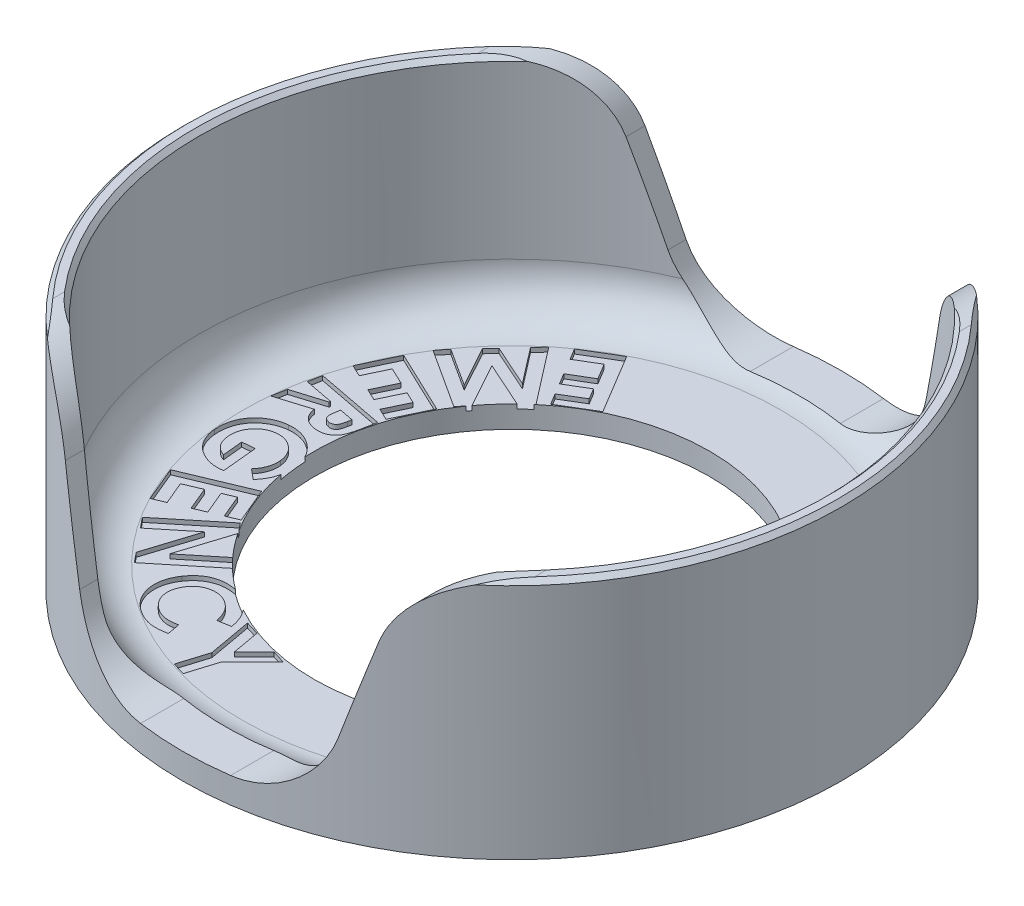
SolidWorks part; units mm, degrees
ref_plane "Front Plane" through (0, 0, 0) normal (0, 0, 1) x (1, 0, 0)
ref_plane "Top Plane" through (0, 0, 0) normal (0, 1, 0) x (1, 0, 0)
ref_plane "Right Plane" through (0, 0, 0) normal (1, 0, 0) x (0, 0, -1)
sketch "Sketch1" plane through (0, 0, 0) normal (0, 1, 0) x (1, 0, 0)
  circle A0 centre (0, 0) radius 37.5
  circle A1 centre (0, 0) radius 22.5
  dimension "D1" = 75
  dimension "D2" = 45
extrude "Boss-Extrude1" add sketch "Sketch1" along normal blind 2.5
sketch "Sketch2" plane through (0, 2.5, 0) normal (0, 1, 0) x (1, 0, 0)
  circle A0 centre (0, 0) radius 35.6108
  circle A1 centre (0, 0) radius 37.5
extrude "Boss-Extrude2" add sketch "Sketch2" along normal blind 25
fillet "Fillet1" radius 5 1 edges at (0, 2.5, 35.6108)
chamfer "Chamfer1" distance 0.5 angle 45 2 edges at (0, 27.5, 37.5) (0, 27.5, 35.6108)
sketch "Sketch3" plane through (0, 0, 0) normal (0, 0, 1) x (1, 0, 0)
  line L1 (-20, 27.5) -> (-17.9393, 27.5)
  line L3 (20, 27.5) -> (12.5381, 2.9295)
  line L7 (-12.5381, 2.9295) -> (-20, 27.5)
  line L8 (36.1108, 27.5) -> (-36.1108, 27.5) construction
  line L11 (-12.5381, 2.9295) -> (12.5381, 2.9295)
  line L12 (17.9393, 27.5) -> (20, 27.5)
  line L13 (-17.9393, 27.5) -> (17.9393, 27.5)
  point P4 (0, 27.5)
  point P6 (0, 0)
  point P12 (0, 27)
  point P15 (0, 27.5)
extrude "Cut-Extrude2" cut sketch "Sketch3" against normal mid plane 109
fillet "Fillet2" radius 10 8 edges at (20, 27.5, -30.5976) (-20, 27.5, -30.5976) (-12.5381, 2.9295, -32.7379) (12.5381, 2.9295, -32.7379) (12.5381, 2.9295, 32.7379) (20, 27.5, 30.5976) (-12.5381, 2.9295, 32.7379) (-20, 27.5, 30.5976)
sketch "Sketch4" plane through (0, 2.5, 0) normal (0, 1, 0) x (1, 0, 0)
  text T0 "<b>                         EMERGENCY    </b>" font "Century Gothic" height in points 30
  text T1 "<b>  STOP</b>" font "Century Gothic" height in points 30
extrude "Cut-Extrude3" cut sketch "Sketch4" against normal blind 0.5
